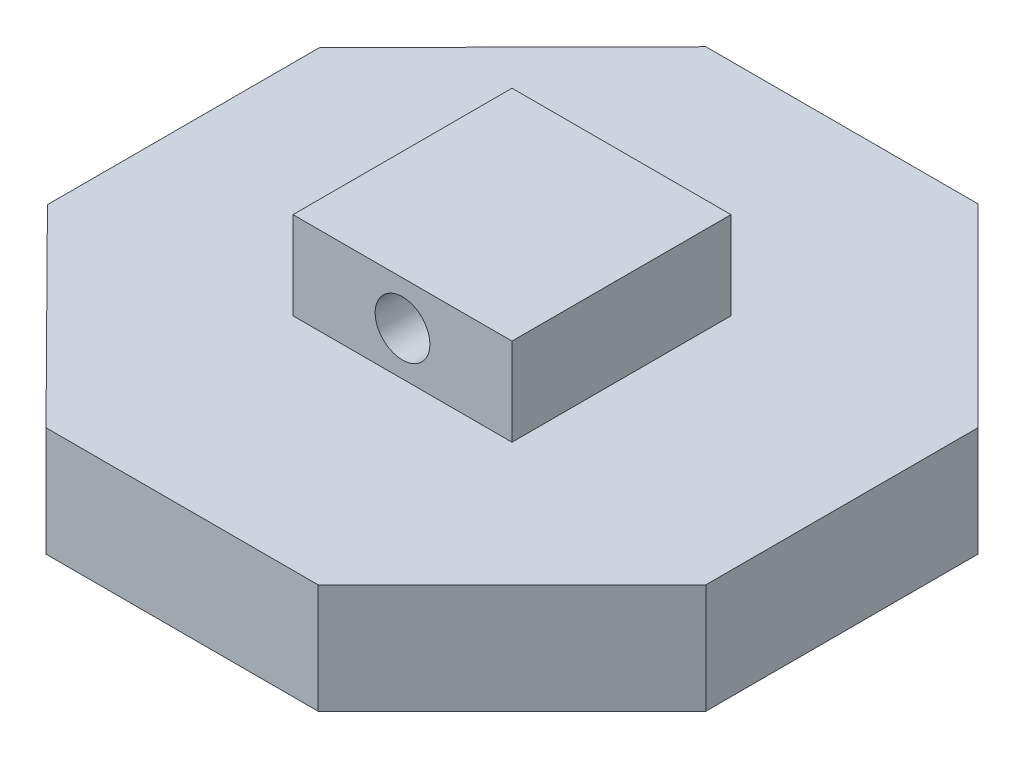
SolidWorks part; units mm, degrees
ref_plane "Front Plane" through (0, 0, 0) normal (0, 0, 1) x (1, 0, 0)
ref_plane "Top Plane" through (0, 0, 0) normal (0, 1, 0) x (1, 0, 0)
ref_plane "Right Plane" through (0, 0, 0) normal (1, 0, 0) x (0, 0, -1)
sketch "Sketch2" plane through (0, 0, 0) normal (0, 1, 0) x (1, 0, 0)
  line L4 (-60, -24.8528) -> (-24.8528, -60.2623)
  line L5 (-24.8528, -60.2623) -> (24.8528, -60.2623)
  line L6 (24.8528, -60.2623) -> (60.2623, -24.8528)
  line L7 (60.2623, -24.8528) -> (60.2623, 24.8528)
  line L8 (24.8528, 60.2623) -> (60.2623, 24.8528)
  line L9 (-24.8528, 60.2623) -> (24.8528, 60.2623)
  line L10 (-60, 24.8528) -> (-24.8528, 60.2623)
  line L11 (-60, 24.8528) -> (-60, -24.8528)
  point P4 (0, 0)
  point P8 (0, 0)
  point P11 (0, 0)
  point P12 (0, 0)
  point P15 (0, 0)
  point P18 (-42.4264, -42.5575)
  point P21 (0, -60.2623)
  point P24 (42.5575, -42.5575)
  point P27 (60.2623, 0)
  point P30 (42.5575, 42.5575)
  point P33 (0, 60.2623)
  point P36 (-42.4264, 42.5575)
  point P39 (-60, 0)
  dimension "D5" = 135.213
  dimension "D6" = 135.213
  dimension "D8" = 225
  dimension "D10" = 135
  dimension "D11" = 49.7056
extrude "Boss-Extrude2" add sketch "Sketch2" along normal blind 20
sketch "Sketch3" plane through (0, 20, 0) normal (0, 1, 0) x (1, 0, 0)
  line L5 (-20, 20) -> (20, 20)
  line L6 (-20, 20) -> (-20, -20)
  line L7 (-20, -20) -> (20, -20)
  line L8 (20, 20) -> (20, -20)
  line L9 (-20, 20) -> (20, -20) construction
  line L10 (-20, -20) -> (20, 20) construction
  point P0 (0, 0)
  point P4 (0, 0)
extrude "Boss-Extrude3" add sketch "Sketch3" along normal blind 16
sketch "Sketch4" plane through (0, 0, 20) normal (0, 0, 1) x (1, 0, 0)
  line L0 (0, 0) -> (0, 36) construction
  line L2 (-10, 28) -> (30, 28) construction
  circle A0 centre (0, 28) radius 5
  point P3 (0, 0)
  point P4 (0, 0)
  point P13 (0, 0)
extrude "Cut-Extrude1" cut sketch "Sketch4" against normal through all both and the other way through all
